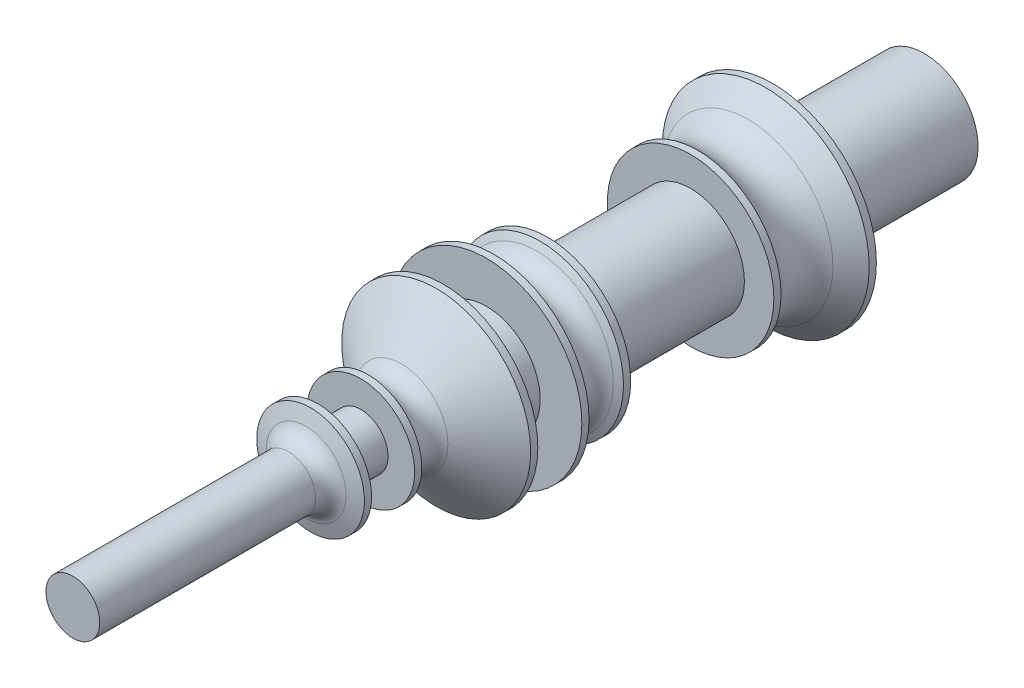
SolidWorks part; units mm, degrees
ref_plane "Front Plane" through (0, 0, 0) normal (0, 0, 1) x (1, 0, 0)
ref_plane "Top Plane" through (0, 0, 0) normal (0, 1, 0) x (1, 0, 0)
ref_plane "Right Plane" through (0, 0, 0) normal (1, 0, 0) x (0, 0, -1)
sketch "Sketch1" plane through (0, 0, 0) normal (0, 0, 1) x (1, 0, 0)
  circle A0 centre (0, 0) radius 15
  dimension "D1" = 30
extrude "Boss-Extrude1" add sketch "Sketch1" along normal blind 235
sketch "Sketch2" plane through (0, 0, 0) normal (0, 1, 0) x (1, 0, 0)
  line L0 (0, -112.5482) -> (0, -13.4988)
  line L4 (15, -235) -> (15, 0) construction
  line L5 (15, -39.9) -> (28.8454, -39.9)
  line L6 (28.8454, -39.9) -> (28.8454, -41.9)
  line L7 (28.8454, -41.9) -> (16.2691, -53.9052)
  line L9 (16.2691, -53.9052) -> (23.2038, -60.84)
  line L10 (23.2038, -60.84) -> (23.2038, -62.84)
  line L11 (23.2038, -62.84) -> (7.5, -62.84)
  line L13 (7.5, -62.84) -> (7.5, -102.74)
  line L14 (7.5, -102.74) -> (23.2038, -102.74)
  line L15 (23.2038, -102.74) -> (23.2038, -104.74)
  line L16 (23.2038, -104.74) -> (7.5, -112.5482)
  line L17 (7.5, -112.5482) -> (0, -112.5482)
  line L18 (15, -39.9) -> (11.1199, -39.9)
  line L19 (11.1199, -39.9) -> (11.1199, -13.4988)
  line L20 (11.1199, -13.4988) -> (0, -13.4988)
  dimension "D2" = 2
  dimension "D3" = 22.94
  dimension "D4" = 2
  dimension "D5" = 39.9
  dimension "D6" = 2
revolve "Revolve1" add sketch "Sketch2" angle 360 about L0
fillet "Fillet2" radius 10 2 edges at (-15, 0, 108.8191) (16.2691, 0, 53.9052)
sketch "Sketch3" plane through (0, 0, 0) normal (1, 0, 0) x (0, 0, -1)
  line L0 (-130.74, 0) -> (-130.74, 14)
  line L1 (-130.74, 14) -> (-128.74, 14)
  line L2 (-128.74, 14) -> (-119.9278, 0)
  line L3 (-119.9278, 0) -> (-130.74, 0)
  line L4 (-102.74, -23.2038) -> (-102.74, 23.2038) construction
  dimension "D1" = 28
  dimension "D2" = 2
  dimension "D3" = 14
revolve "Revolve2" add sketch "Sketch3" angle 360 about L3
sketch "Sketch4" plane through (0, 0, 0) normal (1, 0, 0) x (0, 0, -1)
  line L0 (-235, 15) -> (-235, -15) construction
  line L1 (-235, -7.5) -> (-130.74, -7.5)
  line L2 (-235, -7.5) -> (-235, -30.1946)
  line L3 (-235, -30.1946) -> (-130.74, -30.1946)
  line L4 (-130.74, -7.5) -> (-130.74, -30.1946)
  line L5 (-235, 0) -> (49.9311, 0) construction
  dimension "D1" = 7.5
revolve "Cut-Revolve1" cut sketch "Sketch4" angle 360 about L5
sketch "Sketch6" plane through (0, 0, 0) normal (0, 1, 0) x (1, 0, 0)
  line L0 (0, -147.74) -> (0, -173.4822)
  line L2 (-7.5896, -166.74) -> (-15, -166.74)
  line L4 (-15, -168.74) -> (0, -173.4822)
  line L5 (23.2038, -102.74) -> (-23.2038, -102.74) construction
  line L6 (-7.5896, -154.74) -> (-15, -154.74)
  line L7 (-15, -154.74) -> (-15, -152.74)
  line L8 (-15, -152.74) -> (0, -147.74)
  line L9 (-7.5896, -166.74) -> (-7.5896, -154.74)
  line L10 (-15, -166.74) -> (-15, -168.74)
  dimension "D1" = 64
  dimension "D2" = 2
  dimension "D3" = 15
  dimension "D4" = 12
  dimension "D5" = 2
  dimension "D6" = 7
revolve "Revolve4" add sketch "Sketch6" angle 360 about L0
sketch "Sketch8" plane through (0, 0, 0) normal (1, 0, 0) x (0, 0, -1)
  line L0 (-152.74, 0) -> (-103.74, 0)
  line L1 (-131.74, 7.3477) -> (-131.74, 26.3268)
  line L2 (-131.74, 26.3268) -> (-133.74, 26.3268)
  line L3 (-133.74, 26.3268) -> (-152.74, 0)
  line L4 (-152.74, 15) -> (-152.74, -15) construction
  line L5 (-119.74, 7.3477) -> (-119.74, 26.5955)
  line L6 (-119.74, 26.5955) -> (-117.74, 26.5955)
  line L7 (-117.74, 26.5955) -> (-103.74, 0)
  line L8 (-102.74, -23.2038) -> (-102.74, 23.2038) construction
  line L12 (-131.74, 7.3477) -> (-119.74, 7.3477)
  dimension "D1" = 12
  dimension "D2" = 2
  dimension "D3" = 2
  dimension "D4" = 17
revolve "Revolve5" add sketch "Sketch8" angle 360 about L0
sketch "Sketch9" plane through (0, 0, 0) normal (0, 1, 0) x (1, 0, 0)
  line L0 (-15, -119.74) -> (-15, -131.74)
  line L5 (-26.5955, -119.74) -> (-26.5955, -131.74)
  line L6 (-26.5955, -131.74) -> (-15, -131.74)
  line L7 (26.3268, -131.74) -> (-26.3268, -131.74) construction
  line L8 (-26.5955, -119.74) -> (-15, -119.74)
  line L9 (0, -75.9892) -> (0, -156.1064) construction
sketch "Sketch10" plane through (0, 0, 130.74) normal (0, 0, 1) x (1, 0, 0)
  circle A1 centre (0, 0) radius 15
  circle A2 centre (0, 0) radius 15
  dimension "D1" = 0
extrude "Boss-Extrude2" add sketch "Sketch10" along normal blind 10
scale "Scale1" scale about centroid uniform scaling yes scale factor 1.9329
sketch "Sketch11" plane through (0, 0, -82.2797) normal (0, 0, -1) x (-1, 0, 0)
  circle A1 centre (0, 0) radius 28.9935
  circle A2 centre (0, 0) radius 28.9935
  dimension "D1" = 0
extrude "Boss-Extrude3" add sketch "Sketch11" along normal blind 40
fillet "Fillet3" radius 10 1 edges at (29.9562, 0, 134.0084)
fillet "Fillet5" radius 10 1 edges at (-14.4967, 0, 248.4609)
fillet "Fillet6" radius 10 1 edges at (14.4968, 0, 208.1191)
fillet "Fillet7" radius 10 1 edges at (-14.4968, 0, 202.4891)
scale "Scale2" scale about centroid uniform scaling yes scale factor 1.5
sketch "Sketch12" plane through (0, 0, -220.4804) normal (0, 0, -1) x (-1, 0, 0)
  circle A1 centre (0, 0) radius 43.4903
  circle A2 centre (0, 0) radius 43.4903
  dimension "D1" = 0
extrude "Cut-Extrude1" cut sketch "Sketch12" against normal blind 33.3698
sketch "Sketch13" plane through (0, 0, -187.1106) normal (0, 0, -1) x (-1, 0, 0)
  circle A1 centre (0, 0) radius 43.4903
  circle A2 centre (0, 0) radius 43.4903
  dimension "D1" = 0
extrude "Cut-Extrude2" cut sketch "Sketch13" against normal blind 20
